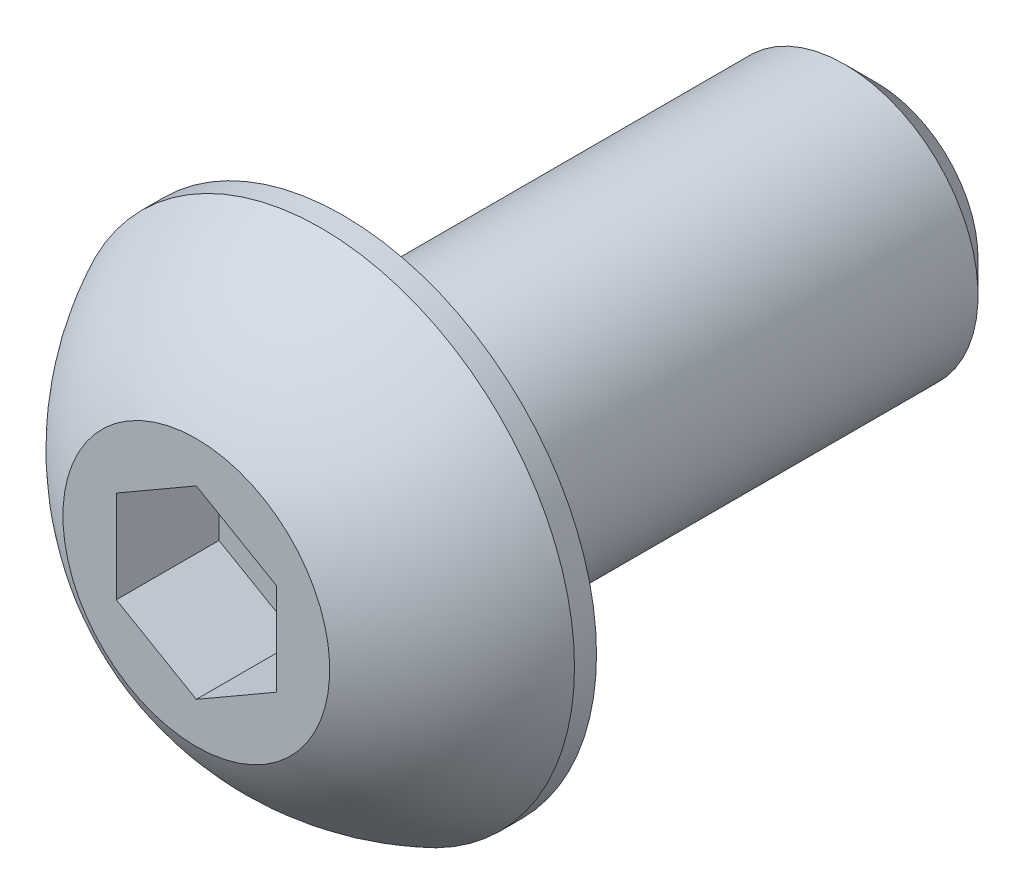
SolidWorks part; units mm, degrees
ref_plane "Front" through (0, 0, 0) normal (0, 0, 1) x (1, 0, 0)
ref_plane "Top" through (0, 0, 0) normal (0, 1, 0) x (1, 0, 0)
ref_plane "Right" through (0, 0, 0) normal (1, 0, 0) x (0, 0, -1)
sketch "Sketch1" plane through (0, 0, 0) normal (1, 0, 0) x (0, 0, -1)
  line L2 (2.75, 2.5) -> (12.75, 2.5)
  line L3 (12.75, 2.5) -> (12.75, 0)
  line L4 (12.75, 0) -> (2.75, 0)
  line L6 (2.3375, 4.75) -> (2.75, 4.75) construction
  line L7 (12.75, 2.5) -> (12.75, -2.5) construction
  line L8 (0, 0) -> (2.75, 0) construction
  line L9 (2.75, 4.75) -> (2.75, -4.75) construction
  line L11 (2.75, 2.5) -> (2.75, 0)
  line L13 (0, 1.5) -> (0, -1.5) construction
  line L14 (0, 1.5) -> (0, 2.5) construction
  arc A3 (0, 2.5) -> (2.3375, 4.75) centre (4.6581, 0) cw construction
  dimension "D1" = 0.4125
revolve "Revolve1" add sketch "Sketch1" angle 360 mid plane about L4
sketch "Sketch3" plane through (0, 0, -12.75) normal (0, 0, -1) x (-1, 0, 0)
  circle A0 centre (0, 0) radius 2.5
curve "Helix/Spiral1" [suppressed] pitch 0.8 height 10.8 turns 13.5
chamfer "Chamfer1" distance 0.6 angle 45 1 edges at (0, 2.5, -12.75)
sketch "Sketch7" plane through (0, 0, 0) normal (1, 0, 0) x (0, 0, -1)
  line L6 (2.3375, 4.75) -> (2.75, 4.75) construction
  line L8 (0, 0) -> (2.75, 0) construction
  line L11 (2.75, 4.75) -> (2.75, -4.75) construction
  line L12 (2.3375, 4.75) -> (2.75, 4.75)
  line L13 (0, 0) -> (2.75, 0)
  line L14 (0, 1.5) -> (0, -1.5) construction
  line L15 (2.75, 4.75) -> (2.75, 0)
  line L16 (0, 2.5) -> (0, 0)
  arc A2 (2.3375, 4.75) -> (0, 2.5) centre (4.6581, 0) ccw construction
  arc A3 (2.3375, 4.75) -> (0, 2.5) centre (4.6581, 0) ccw
revolve "Revolve2" add sketch "Sketch7" angle 360 mid plane about L13
sketch "Sketch5" plane through (0, 0, 0) normal (0, 0, 1) x (1, 0, 0)
  line L1 (1.5, -0.866) -> (1.5, 0.866)
  line L2 (1.5, 0.866) -> (0, 1.7321)
  line L3 (0, 1.7321) -> (-1.5, 0.866)
  line L4 (-1.5, 0.866) -> (-1.5, -0.866)
  line L5 (-1.5, -0.866) -> (0, -1.7321)
  line L6 (0, -1.7321) -> (1.5, -0.866)
  circle A0 centre (0, 0) radius 1.5 construction
extrude "Cut-Extrude2" cut sketch "Sketch5" against normal blind 1.925
sketch "Sketch6" plane through (0, 0, 0) normal (0, 0, 1) x (1, 0, 0)
  circle A0 centre (0, 0) radius 1.7321
extrude "Cut-Extrude3" [suppressed] cut sketch "Sketch6" against normal blind 1.925 draft 45
sketch "Sketch2" plane through (0, 0, 0) normal (1, 0, 0) x (0, 0, -1)
  line L0 (12.15, 2.5) -> (12.85, 2.5)
  line L1 (12.85, 2.5) -> (12.55, 1.9804)
  line L2 (12.55, 1.9804) -> (12.45, 1.9804)
  line L3 (12.45, 1.9804) -> (12.15, 2.5)
  line L4 (12.3, 2.2402) -> (12.7, 2.2402) construction
  dimension "D1" = 60
  dimension "D2" = 0.1
  dimension "D3" = 0.4
sweep "Cut-Sweep1" [suppressed] cut profiles "Sketch2" path "Helix/Spiral1"
sketch "Sketch10" plane through (0, 0, 0) normal (1, 0, 0) x (0, 0, -1)
  line L0 (12.75, 2.5) -> (12.75, -2.5) construction
  point P0 (11.55, -2.5)
  dimension "D1" = 1.2
ref_axis "Center Axis 1" through (0, 0, -8.1113) along (0, 0, 1)
ref_plane "Contact Plane 1" through (0, 0, -2.75) normal (0, 0, -1) x (-1, 0, 0)
ref_plane "Contact Plane 2" through (0, 0, 0) normal (0, 0, 1) x (1, 0, 0)
equation "\"D3@Helix/Spiral1\" = \"Lg@Sketch1\" + \"D4@Helix/Spiral1\""
equation "\"D2@Sketch2\" = \"D4@Helix/Spiral1\" * .125"
equation "\"D3@Sketch2\" = \"D4@Helix/Spiral1\" * .5"
equation "\"D1@Chamfer1\" = \"D4@Helix/Spiral1\" * .75"
equation "\"D1@Cut-Extrude2\" = \"Head Ht@Sketch1\" * .7"
equation "\"D1@Sketch1\" = \"Head Ht@Sketch1\" * .15"
equation "\"D1@Sketch10\" = \"D4@Helix/Spiral1\" * 1.5"
equation "\"D1@Cut-Extrude3\" = \"D1@Cut-Extrude2\""
